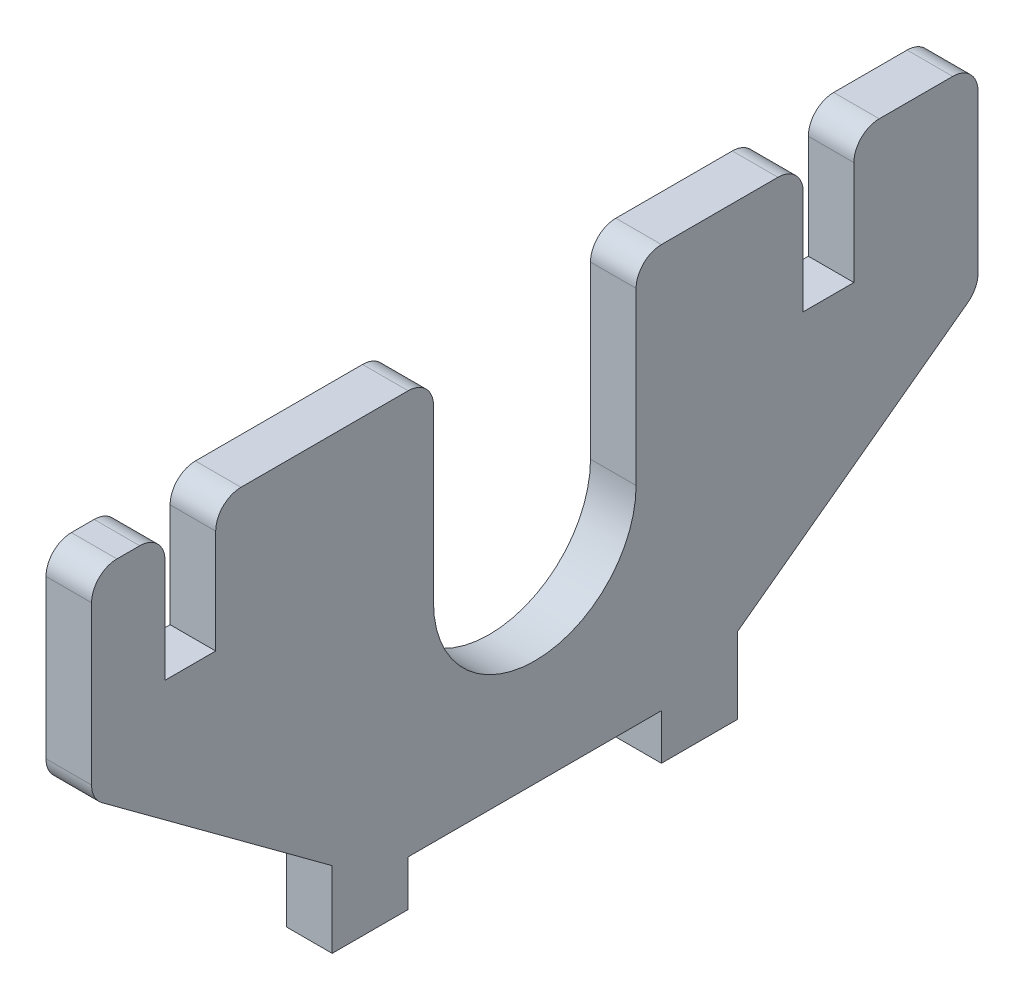
SolidWorks part; units mm, degrees
ref_plane "Front Plane" through (0, 0, 0) normal (0, 0, 1) x (1, 0, 0)
ref_plane "Top Plane" through (0, 0, 0) normal (0, 1, 0) x (1, 0, 0)
ref_plane "Right Plane" through (0, 0, 0) normal (1, 0, 0) x (0, 0, -1)
sketch "Sketch1" plane through (0, 0, 0) normal (0, 1, 0) x (1, 0, 0)
  line L0 (-450, 300) -> (-400, 300)
  line L1 (-400, 300) -> (-200, 250)
  line L2 (-200, 250) -> (200, 250) construction
  line L3 (200, 250) -> (600, 40) construction
  line L4 (600, 40) -> (1200, 40)
  line L5 (-450, -300) -> (-400, -300)
  line L6 (-400, -300) -> (-200, -250)
  line L7 (-200, -250) -> (200, -250) construction
  line L8 (200, -250) -> (600, -40) construction
  line L9 (600, -40) -> (1200, -40)
  line L10 (600, 40) -> (600, -40) construction
  line L11 (200, -250) -> (200, 250) construction
  line L12 (-200, 250) -> (-200, -250) construction
  line L13 (-400, -300) -> (-400, 300) construction
  line L14 (0, 0) -> (200, 0) construction
  line L15 (0, 250) -> (0, 0) construction
  line L16 (1200, 40) -> (1200, -40)
  line L17 (-450, 300) -> (-450, -300)
  line L18 (600, 0) -> (200, 0) construction
  line L19 (-450, 0) -> (-400, 0) construction
  line L20 (-400, 0) -> (-200, 0) construction
  line L21 (-200, 0) -> (0, 0) construction
  line L22 (-200, 250) -> (600, 40)
  line L23 (600, -40) -> (-200, -250)
  dimension "D1" = 600
  dimension "D2" = 200
  dimension "D3" = 50
  dimension "D4" = 400
  dimension "D5" = 500
  dimension "D6" = 80
  dimension "D7" = 600
  dimension "D8" = 400
extrude "Boss-Extrude1" add sketch "Sketch1" along normal blind 15
sketch "Sketch2" plane through (0, 0, 0) normal (0, 0, 1) x (1, 0, 0)
  line L0 (-450, 0) -> (-450, -40)
  line L1 (-450, -40) -> (-400, -40)
  line L2 (-400, -40) -> (-400, 0)
  line L3 (-400, 0) -> (-200, 0) construction
  line L4 (-400, 0) -> (-450, 0)
  line L5 (-440, -15) -> (-440, -40)
  line L6 (-410, -15) -> (-410, -40)
  line L7 (-425, 0) -> (-425, -15) construction
  circle A0 centre (-425, -15) radius 15
  dimension "D1" = 30
  dimension "D2" = 40
extrude "Boss-Extrude2" add sketch "Sketch2" along normal up to surface and the other way up to surface contours L4 L7 A0 L6 L1 L2 | L7 L4 L0 L1 L5 A0 region at (-444.1006, -18.2067, 0) region at (-405.8994, -18.2067, 0) up to face at (-425, 7.5, 300) other way up to face at (-425, 7.5, -300)
sketch "Sketch4" plane through (0, 0, 0) normal (0, 1, 0) x (1, 0, 0)
  line L0 (-450, 230) -> (-400, 230)
  line L1 (-450, 300) -> (-450, -300) construction
  line L2 (-400, 230) -> (-150, 167.5)
  line L3 (-150, 167.5) -> (-150, -167.5)
  line L4 (-150, -167.5) -> (-400, -230)
  line L5 (-400, -230) -> (-450, -230)
  line L6 (-400, 230) -> (-400, -230) construction
  line L7 (-200, 250) -> (-200, -250) construction
  line L9 (-200, 0) -> (-150, 0) construction
  line L10 (-400, -230) -> (-400, -300) construction
  line L11 (-400, -300) -> (-200, -250) construction
  line L12 (-450, 230) -> (-450, -230)
  line L14 (-200, 250) -> (-400, 300) construction
  line L15 (-100, 155) -> (-100, -155)
  line L16 (-100, -155) -> (520, 0)
  line L17 (520, 0) -> (-100, 155)
  line L18 (520, 0) -> (-100, 0) construction
  dimension "D1" = 460
  dimension "D2" = 300
  dimension "D3" = 50
extrude "Cut-Extrude2" cut sketch "Sketch4" against normal through all both and the other way through all
sketch "Sketch5" plane through (0, 0, 0) normal (1, 0, 0) x (0, 0, -1)
  line L0 (-300, 0) -> (-230, 0) construction
  line L1 (-285, 0) -> (-245, 0)
  line L2 (-285, 0) -> (-285, -40)
  line L3 (-285, -40) -> (-245, -40)
  line L4 (-245, 0) -> (-245, -40)
  line L5 (-300, -40) -> (-230, -40) construction
  line L6 (230, 0) -> (300, 0) construction
  line L7 (245, 0) -> (285, 0)
  line L8 (245, 0) -> (245, -40)
  line L9 (245, -40) -> (285, -40)
  line L10 (285, 0) -> (285, -40)
  line L11 (230, -40) -> (300, -40) construction
  line L12 (-300, 0) -> (-300, -40) construction
  line L13 (230, -40) -> (230, 0) construction
  line L14 (300, 0) -> (300, -40) construction
  dimension "D1" = 15
  dimension "D2" = 15
  dimension "D3" = 15
  dimension "D4" = 15
extrude "Cut-Extrude3" cut sketch "Sketch5" against normal through all
sketch "Sketch7" plane through (1200, 0, 0) normal (1, 0, 0) x (0, 0, -1)
  line L1 (-40, 15) -> (-87.5, 50)
  line L2 (-87.5, 50) -> (-87.5, 88.7)
  line L3 (-87.5, 88.7) -> (87.5, 88.7)
  line L4 (87.5, 88.7) -> (87.5, 50)
  line L5 (87.5, 50) -> (40, 15)
  line L7 (-40, 15) -> (40, 15)
  line L8 (-20, 50) -> (-20, 88.7)
  line L9 (87.5, 50) -> (-87.5, 50) construction
  line L10 (0, 88.7) -> (0, 50) construction
  line L11 (-20, 88.7) -> (20, 88.7)
  line L12 (0, 50) -> (0, 0) construction
  line L13 (20, 88.7) -> (20, 50)
  line L14 (-73, 88.7) -> (-63, 88.7)
  line L15 (-73, 88.7) -> (-73, 63.2)
  line L16 (-73, 63.2) -> (-63, 63.2)
  line L17 (-63, 88.7) -> (-63, 63.2)
  line L18 (53, 88.7) -> (63, 88.7)
  line L19 (53, 88.7) -> (53, 63.2)
  line L20 (53, 63.2) -> (63, 63.2)
  line L21 (63, 88.7) -> (63, 63.2)
  circle A0 centre (0, 50) radius 20
  line M14 (40, 15) -> (-40, 15)
  dimension "D3" = 40
  dimension "D1" = 175
  dimension "D2" = 50
  dimension "D4" = 25.5
  dimension "D5" = 10
  dimension "D6" = 63
  dimension "D7" = 53
  dimension "D8" = 38.7
extrude "Boss-Extrude4" add sketch "Sketch7" against normal blind 75 contours L3 L21 L20 L19 L17 L16 L15 L2 L1 L5 L4 M14 region at (1200, 34.0287, 62.6236)
sketch "Sketch8" plane through (0, 0, 0) normal (0, 0, 1) x (1, 0, 0)
  line L0 (1125, 88.7) -> (1200, 88.7) construction
  line L1 (1140, 88.7) -> (1185, 88.7)
  line L2 (1140, 88.7) -> (1140, 15)
  line L3 (1140, 15) -> (1185, 15)
  line L4 (1185, 88.7) -> (1185, 15)
  line L5 (1125, 15) -> (1200, 15) construction
  line L6 (1125, 50) -> (1125, 88.7) construction
  line L7 (1200, 50) -> (1200, 88.7) construction
  line L8 (1155, 88.7) -> (1170, 88.7) construction
  line L9 (1155, 88.7) -> (1170, 88.7)
  line L10 (1155, 88.7) -> (1155, 15)
  line L11 (1155, 15) -> (1170, 15)
  line L12 (1170, 88.7) -> (1170, 15)
  line L15 (1162.5, 50) -> (1162.5, 88.7) construction
  line L16 (1125, 50) -> (1200, 50) construction
  line L17 (1155, 88.7) -> (1170, 88.7) construction
  dimension "D1" = 15
  dimension "D2" = 15
  dimension "D3" = 15
extrude "Cut-Extrude4" cut sketch "Sketch8" against normal through all both and the other way through all contours L10 L1 L2 L3 | L1 L12 L3 L4 region at (1147.5, 51.85, 0) region at (1177.5, 51.85, 0)
fillet "Fillet1" radius 5 53 edges at (1192.5, 50, 87.5) (1162.5, 50, 87.5) (1132.5, 50, 87.5) (1192.5, 50, -87.5) (1162.5, 50, -87.5) (1132.5, 50, -87.5) (1192.5, 88.7, -87.5) (1162.5, 88.7, -87.5) (1132.5, 88.7, -87.5) (1132.5, 88.7, -63) (1162.5, 88.7, -63) (1192.5, 88.7, -63) (1192.5, 88.7, -53) (1162.5, 88.7, -53) (1132.5, 88.7, -53) (1192.5, 88.7, -20) (1162.5, 88.7, -20) (1132.5, 88.7, -20) (1192.5, 88.7, 63) (1162.5, 88.7, 63) (1132.5, 88.7, 63) (1132.5, 88.7, 87.5) (1162.5, 88.7, 87.5) (1192.5, 88.7, 87.5) (1192.5, 88.7, 73) (1162.5, 88.7, 73) (1132.5, 88.7, 73) (1192.5, 88.7, 20) (1162.5, 88.7, 20) (1132.5, 88.7, 20) (600, 7.5, 40) (600, 7.5, -40) (520, 7.5, 0) (-440, -40, -292.5) (-440, -40, -237.5) (-400, -40, -292.5) (-400, -40, -237.5) (-450, -40, -237.5) (-410, -40, -237.5) (-450, -40, -292.5) (-410, -40, -292.5) (-150, 7.5, 167.5) (-100, 7.5, 155) (-150, 7.5, -167.5) (-100, 7.5, -155) (-450, -40, 237.5) (-410, -40, 237.5) (-440, -40, 237.5) (-400, -40, 237.5) (-450, -40, 292.5) (-440, -40, 292.5) (-400, -40, 292.5) (-410, -40, 292.5)
sketch "Sketch9" plane through (0, 0, 0) normal (0, 1, 0) x (1, 0, 0)
  line L0 (1185, 87.5) -> (1185, 82.5) construction
  line L1 (-450, 300) -> (1185, 300)
  line L2 (-450, 300) -> (-450, -300)
  line L3 (-450, -300) -> (1185, -300)
  line L4 (1185, 300) -> (1185, -300)
extrude "Cut-Extrude5" cut sketch "Sketch9" against normal through all both and the other way through all
sketch "Sketch10" plane through (1200, 0, 0) normal (1, 0, 0) x (0, 0, -1)
  line L0 (-40, 0) -> (40, 0) construction
  line L1 (-25, 0) -> (25, 0)
  line L2 (-25, 0) -> (-25, 15)
  line L3 (-25, 15) -> (25, 15)
  line L4 (25, 0) -> (25, 15)
  line L5 (0, 15) -> (0, 0) construction
  line L6 (-40, 15) -> (-40, 0) construction
  dimension "D1" = 15
  dimension "D2" = 15
extrude "Cut-Extrude6" cut sketch "Sketch10" against normal through all
sketch "Sketch11" plane through (1200, 0, 0) normal (1, 0, 0) x (0, 0, -1)
  line L0 (25, 0) -> (25, 15) construction
  line L1 (-25, 15) -> (25, 15)
  line L2 (-25, 15) -> (-25, 9)
  line L3 (-25, 9) -> (25, 9)
  line L4 (25, 15) -> (25, 9)
  line L5 (25, 0) -> (40, 0) construction
  dimension "D1" = 9
extrude "Boss-Extrude5" add sketch "Sketch11" against normal up to surface (15 mm away) up to face at (1185, 58.2899, 1.7647)
sketch "Sketch12" plane through (0, 0, 0) normal (0, 0, 1) x (1, 0, 0)
  line L0 (1185, 0) -> (1200, 0) construction
  line L1 (1185, 88.7) -> (1191, 88.7)
  line L2 (1185, 88.7) -> (1185, 0)
  line L3 (1185, 0) -> (1191, 0)
  line L4 (1191, 88.7) -> (1191, 0)
  line L5 (1200, 15) -> (1200, 48.5013) construction
  dimension "D1" = 9
extrude "Cut-Extrude7" cut sketch "Sketch12" against normal through all both and the other way through all
